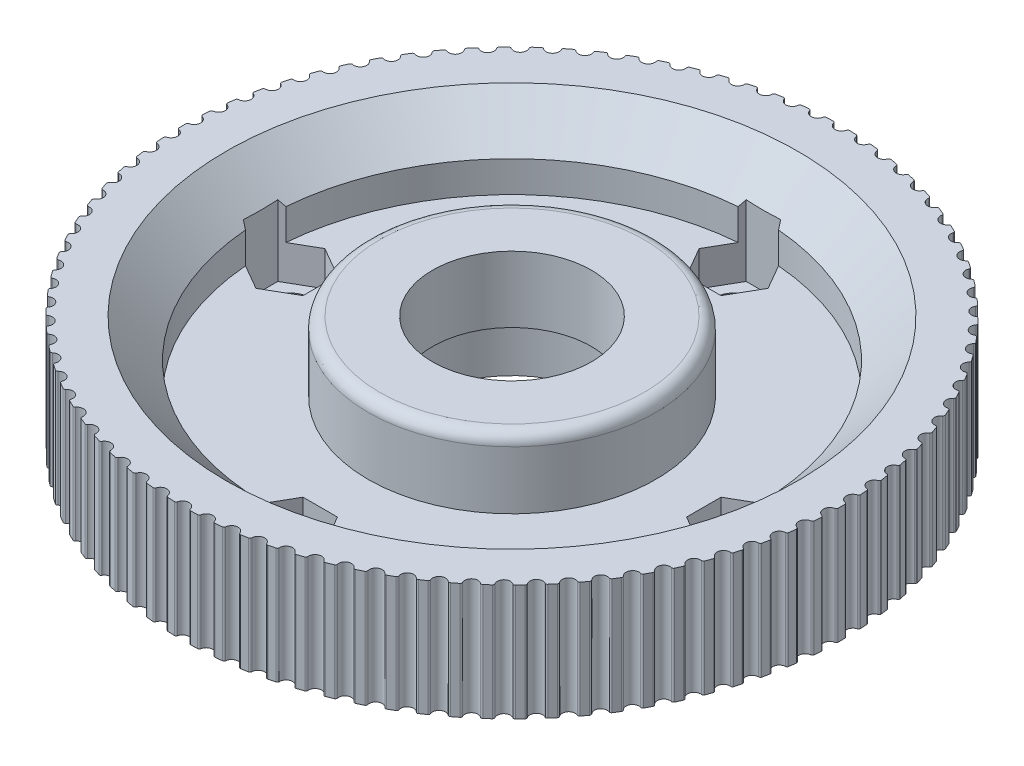
SolidWorks part; units mm, degrees
ref_plane "Front Plane" through (0, 0, 0) normal (0, 0, 1) x (1, 0, 0)
ref_plane "Top Plane" through (0, 0, 0) normal (0, 1, 0) x (1, 0, 0)
ref_plane "Right Plane" through (0, 0, 0) normal (1, 0, 0) x (0, 0, -1)
sketch "Sketch1" plane through (0, 0, 0) normal (0, 1, 0) x (1, 0, 0)
  line L0 (0, 0) -> (0, 29.7426) construction
  circle A0 centre (0, 0) radius 6.85
  circle A1 centre (0, 0) radius 7.85
  circle A2 centre (0, 19.1) radius 1.65
  circle A3 centre (19.1, 0) radius 1.65
  circle A4 centre (0, -19.1) radius 1.65
  circle A5 centre (-19.1, 0) radius 1.65
  arc A6 (-0.6958, 28.3915) -> (0.6958, 28.3915) centre (0, 0) ccw
  arc A7 (-0.5459, 28.275) -> (0.5459, 28.275) centre (0, 28.4) ccw
  arc A9 (0.6958, 28.3915) -> (0.5459, 28.275) centre (0.6921, 28.2415) ccw
  arc A11 (-0.6958, 28.3915) -> (-0.5459, 28.275) centre (-0.6921, 28.2415) cw
  point P16 (0, 0)
  dimension "D1" = 19.1
  dimension "D3" = 56.8
  dimension "D4" = 3.3
  dimension "D5" = 1.12
  dimension "D6" = 13.7
  dimension "D7" = 15.7
  dimension "D2" = 4
extrude "Boss-Extrude1" add sketch "Sketch1" along normal blind 10 contours A1 A2 A7 A11 A6 A9 A5 A4 A3 | A0 A1 region at (-7.628, 0, 0) region at (-1.0929, 0, -27.7257)
ref_axis "Axis1" through (0, 10, 0) along (0, -1, 0)
pattern_circular "CirPattern1" count 90 over 360 about axis through (0, 10, 0) along (0, -1, 0) of face at (-0.6104, 5, -28.3466) of face at (0, 5, -28.0575) of face at (0.6104, 5, -28.3466)
extrude "Cut-Extrude1" cut sketch "Sketch1<3>" along normal blind 4.3 contours A1
sketch "Sketch1<3>" plane through (0, 0, 0) normal (0, 1, 0) x (1, 0, 0) same geometry as "Sketch1"
sketch "Sketch2" plane through (0, 10, 0) normal (0, 1, 0) x (1, 0, 0)
  line L0 (19.1, 2.97) -> (16.5279, 1.485)
  line L1 (-2.97, 19.1) -> (-1.485, 16.5279)
  line L2 (-1.485, 16.5279) -> (1.485, 16.5279)
  line L3 (1.485, 16.5279) -> (2.97, 19.1)
  line L4 (2.97, 19.1) -> (1.485, 21.6721)
  line L5 (1.485, 21.6721) -> (-1.485, 21.6721)
  line L6 (-1.485, 21.6721) -> (-2.97, 19.1)
  line L7 (21.6721, 1.485) -> (19.1, 2.97)
  line L8 (21.6721, -1.485) -> (21.6721, 1.485)
  line L9 (19.1, -2.97) -> (21.6721, -1.485)
  line L10 (16.5279, -1.485) -> (19.1, -2.97)
  line L11 (16.5279, 1.485) -> (16.5279, -1.485)
  line L12 (2.97, -19.1) -> (1.485, -16.5279)
  line L13 (1.485, -21.6721) -> (2.97, -19.1)
  line L14 (-1.485, -21.6721) -> (1.485, -21.6721)
  line L15 (-2.97, -19.1) -> (-1.485, -21.6721)
  line L16 (-1.485, -16.5279) -> (-2.97, -19.1)
  line L17 (1.485, -16.5279) -> (-1.485, -16.5279)
  line L18 (-19.1, -2.97) -> (-16.5279, -1.485)
  line L19 (-21.6721, -1.485) -> (-19.1, -2.97)
  line L20 (-21.6721, 1.485) -> (-21.6721, -1.485)
  line L21 (-19.1, 2.97) -> (-21.6721, 1.485)
  line L22 (-16.5279, 1.485) -> (-19.1, 2.97)
  line L23 (-16.5279, -1.485) -> (-16.5279, 1.485)
  circle A0 centre (0, 19.1) radius 2.5721 construction
  circle A1 centre (0, 0) radius 23.65
  circle A2 centre (0, 0) radius 21.3
  circle A3 centre (0, 0) radius 12.4
  point P30 (0, 0)
  dimension "D3" = 47.3
  dimension "D4" = 42.6
  dimension "D1" = 2.97
  dimension "D2" = 4
extrude "Cut-Extrude2" cut sketch "Sketch2" against normal blind 9 contours L15 A2 L13 L12 L17 L16 | L21 A2 L19 L18 L23 L22 | L9 A2 L7 L0 L11 L10 | L4 A2 L6 L1 L2 L3 region at (18.9616, 10, 0) region at (0, 10, -18.9616) region at (0, 10, 18.9616) region at (-18.9616, 10, 0)
extrude "Cut-Extrude3" cut sketch "Sketch2<3>" against normal blind 6 contours L13 A2 L9 L10 L11 L0 L7 L4 L3 L2 L1 L6 L21 L22 L23 L18 L19 L15 L16 L17 L12 A3 region at (17.5137, 10, -2.7475)
sketch "Sketch2<3>" plane through (0, 10, 0) normal (0, 1, 0) x (1, 0, 0) same geometry as "Sketch2"
chamfer "Chamfer1" distance 3.32 angle 45 1 edges at (0, 10, 21.3)
fillet "Fillet1" radius 1 1 edges at (0, 10, 12.4)
extrude "Cut-Extrude4" cut sketch "Sketch2<4>" against normal blind 9 contours L14 L13 L12 L17 L16 L15 | L8 L7 L0 L11 L10 L9 | L4 L5 L6 L1 L2 L3 | L21 L20 L19 L18 L23 L22
sketch "Sketch2<4>" plane through (0, 10, 0) normal (0, 1, 0) x (1, 0, 0) same geometry as "Sketch2"
